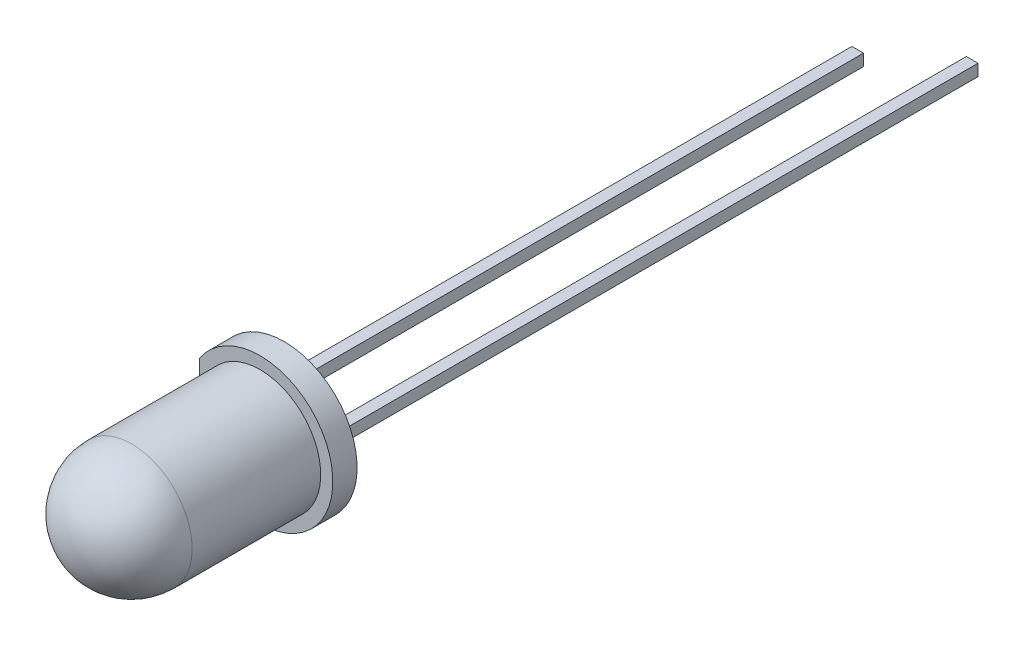
SolidWorks part; units mm, degrees
ref_plane "Plano frontal" through (0, 0, 0) normal (0, 0, 1) x (1, 0, 0)
ref_plane "Plano superior" through (0, 0, 0) normal (0, 1, 0) x (1, 0, 0)
ref_plane "Plano direito" through (0, 0, 0) normal (1, 0, 0) x (0, 0, -1)
sketch "Esboço1" plane through (0, 0, 0) normal (0, 0, 1) x (1, 0, 0)
  circle A0 centre (0, 0) radius 3
  dimension "D1" = 6
extrude "Ressalto-extrusão1" add sketch "Esboço1" along normal blind 1
sketch "Esboço3" plane through (0, 0, 0) normal (1, 0, 0) x (0, 0, -1)
  line L0 (-1, 0) -> (-8.8, 0)
  line L1 (-1, 3) -> (-1, -3) construction
  line L2 (-6.3, 2.5) -> (-1, 2.5)
  line L3 (-1, 0) -> (-1, 2.5)
  arc A0 (-8.8, 0) -> (-6.3, 2.5) centre (-6.3, 0) cw
  dimension "D1" = 2.5
  dimension "D2" = 7.8
revolve "Revolução1" add sketch "Esboço3" angle 360 about L0
sketch "Esboço4" plane through (0, 0, 0) normal (0, 0, -1) x (-1, 0, 0)
  line L0 (2.5, 1.6583) -> (2.5, -1.6583)
  circle A0 centre (0, 0) radius 3 construction
  arc A1 (2.5, -1.6583) -> (2.5, 1.6583) centre (0, 0) ccw
  circle A2 centre (0, 0) radius 2.5 construction
extrude "Corte-extrusão1" cut sketch "Esboço4" against normal up to surface (1 mm away) up to face at (2.5, 0, 1)
sketch "Esboço5" plane through (0, 0, 0) normal (0, 0, -1) x (-1, 0, 0)
  line L0 (-1.12, 0) -> (1.12, 0) construction
  line L1 (-1.6, -0.24) -> (-1.12, -0.24)
  line L2 (-1.6, -0.24) -> (-1.6, 0.24)
  line L3 (-1.6, 0.24) -> (-1.12, 0.24)
  line L4 (-1.12, -0.24) -> (-1.12, 0.24)
  line L5 (1.12, -0.24) -> (1.6, -0.24)
  line L6 (1.12, -0.24) -> (1.12, 0.24)
  line L7 (1.12, 0.24) -> (1.6, 0.24)
  line L8 (1.6, -0.24) -> (1.6, 0.24)
  dimension "D1" = 3.2
  dimension "D2" = 0.48
extrude "Ressalto-extrusão2" add sketch "Esboço5" along normal blind 25 separate body
sketch "Esboço6" plane through (0, 0, -25) normal (0, 0, -1) x (-1, 0, 0)
  line L4 (-1.6, 0.24) -> (-1.6, -0.24)
  line L5 (-1.6, -0.24) -> (-1.12, -0.24)
  line L6 (-1.12, -0.24) -> (-1.12, 0.24)
  line L7 (-1.12, 0.24) -> (-1.6, 0.24)
  line L8 (-1.6, 0.24) -> (-1.6, -0.24)
  line L9 (-1.6, -0.24) -> (-1.12, -0.24)
  line L10 (-1.12, -0.24) -> (-1.12, 0.24)
  line L11 (-1.12, 0.24) -> (-1.6, 0.24)
  dimension "D1" = 0
extrude "Ressalto-extrusão3" add sketch "Esboço6" along normal blind 2 separate body
sketch "Esboço7" plane through (0, 0, 0) normal (0, 1, 0) x (1, 0, 0)
  line L0 (-1.6, 0) -> (-1.6, -3.5)
  line L1 (-1.12, 0) -> (-1.12, -2)
  line L2 (0.02, -2) -> (1.2, -4)
  line L3 (1.2, -4) -> (-1.3, -4)
  line L4 (-1.3, -4) -> (-1.6, -3.5)
  line L5 (-1.12, -2) -> (0.02, -2)
  line L6 (1.6, 0) -> (1.6, -4)
  line L7 (1.6, -4) -> (1.4, -4)
  line L8 (1.4, -4) -> (0.22, -2)
  line L9 (0.22, -2) -> (1.12, -2)
  line L10 (1.12, -2) -> (1.12, 0)
  line L11 (-1.6, 0) -> (-1.12, 0)
  line L12 (1.12, 0) -> (1.6, 0)
  dimension "D1" = 4
  dimension "D2" = 2
  dimension "D3" = 2.8
  dimension "D4" = 0.2
  dimension "D5" = 0.9
  dimension "D6" = 3.5
  dimension "D7" = 2.5
extrude "Corte-extrusão2" cut sketch "Esboço7" against normal mid plane 0.48
sketch "Esboço8" plane through (0, 0, 0) normal (0, 1, 0) x (1, 0, 0)
  line L0 (-1.3, -4) -> (1.2, -4) construction
  line L1 (-1.6, -3.5) -> (-1.3, -4) construction
  line L2 (-1.6, 0) -> (-1.6, -3.5) construction
  line L3 (1.2, -4) -> (0.02, -2) construction
  line L4 (0.02, -2) -> (-1.12, -2) construction
  line L5 (-1.12, -2) -> (-1.12, 0) construction
  line L6 (0.22, -2) -> (1.4, -4) construction
  line L7 (1.12, -2) -> (0.22, -2) construction
  line L8 (1.12, 0) -> (1.12, -2) construction
  line L9 (1.6, -4) -> (1.6, 0) construction
  line L10 (1.4, -4) -> (1.6, -4) construction
  line L11 (-1.12, 0) -> (-1.6, 0) construction
  line L12 (1.6, 0) -> (1.12, 0) construction
  line L13 (-1.3, -4) -> (1.2, -4)
  line L14 (-1.6, -3.5) -> (-1.3, -4)
  line L15 (-1.6, 0) -> (-1.6, -3.5)
  line L16 (1.2, -4) -> (0.02, -2)
  line L17 (0.02, -2) -> (-1.12, -2)
  line L18 (-1.12, -2) -> (-1.12, 0)
  line L19 (0.22, -2) -> (1.4, -4)
  line L20 (1.12, -2) -> (0.22, -2)
  line L21 (1.12, 0) -> (1.12, -2)
  line L22 (1.6, -4) -> (1.6, 0)
  line L23 (1.4, -4) -> (1.6, -4)
  line L24 (-1.12, 0) -> (-1.6, 0)
  line L25 (1.6, 0) -> (1.12, 0)
extrude "Ressalto-extrusão4" add sketch "Esboço8" along normal mid plane 0.48 separate body
combine bodies "Combinar1" operation type add bodies to combine 109 106 104
combine bodies "Combinar2" operation type add bodies to combine 108 105
sketch "Esboço10" plane through (0, 0, 0) normal (0, 1, 0) x (1, 0, 0)
  line L0 (-0.05, -4) -> (-0.05, -3.7)
  line L1 (-1.3, -4) -> (1.2, -4) construction
  line L2 (-0.55, -4) -> (-0.05, -4)
  arc A0 (-0.05, -3.7) -> (-0.55, -4) centre (-0.05, -4.2667) ccw
  dimension "D1" = 0.5
  dimension "D2" = 0.3
revolve "Corte-Revolução1" cut sketch "Esboço10" angle 360 about L0
sketch "Esboço11" plane through (0, 0, 0) normal (0, 1, 0) x (1, 0, 0)
  line L0 (-0.55, -4) -> (-0.05, -4) construction
  line L1 (-0.05, -4) -> (-0.05, -3.7) construction
  line L2 (-0.55, -4) -> (-0.05, -4)
  line L3 (-0.05, -4) -> (-0.05, -3.7)
  arc A0 (-0.05, -3.7) -> (-0.55, -4) centre (-0.05, -4.2667) ccw construction
  arc A1 (-0.05, -3.7) -> (-0.55, -4) centre (-0.05, -4.2667) ccw
revolve "Revolução2" add sketch "Esboço11" angle 360 about L3
combine bodies "Combinar3" operation type add bodies to combine 113 112
sketch "Esboço12" plane through (0, 0, 4) normal (0, 0, 1) x (1, 0, 0)
  circle A0 centre (-0.05, 0) radius 0.2
  arc A1 (0.3886, 0.24) -> (-0.4886, 0.24) centre (-0.05, 0) ccw construction
  dimension "D1" = 0.4
extrude "Corte-extrusão3" cut sketch "Esboço12" against normal blind 0.1
